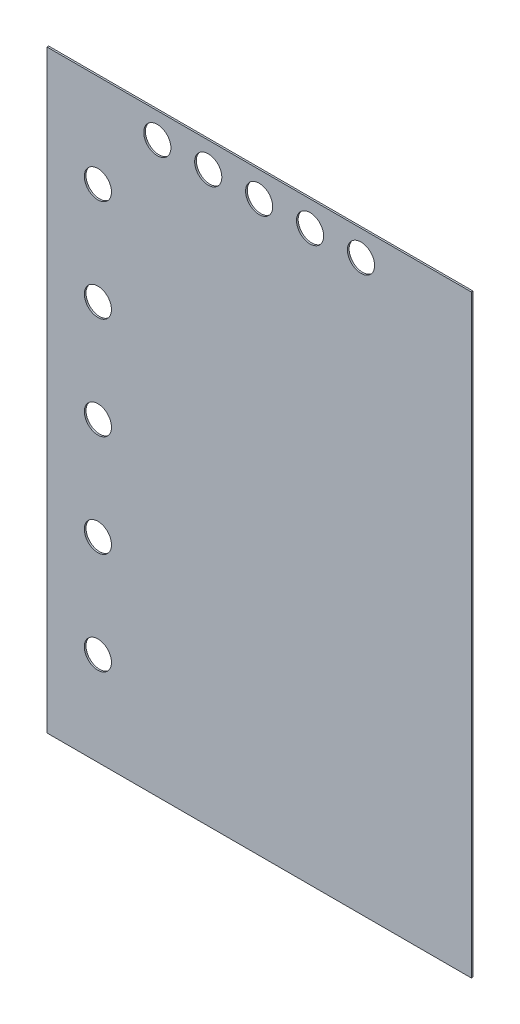
SolidWorks part; units mm, degrees
ref_plane "Front Plane" through (0, 0, 0) normal (1, 0, 0) x (0, 1, 0)
ref_plane "Top Plane" through (0, 0, 0) normal (0, 0, 1) x (0, 1, 0)
ref_plane "Right Plane" through (0, 0, 0) normal (0, 1, 0) x (-1, 0, 0)
sketch "Sketch1" plane through (0, 0, 0) normal (0, 0, 1) x (0, 1, 0)
  line L1 (-175, -125) -> (175, -125)
  line L2 (-175, -125) -> (-175, 125)
  line L3 (-175, 125) -> (175, 125)
  line L4 (175, -125) -> (175, 125)
  line L5 (-175, -125) -> (175, 125) construction
  line L6 (-175, 125) -> (175, -125) construction
  point P0 (0, 0)
  dimension "D1" = 350
  dimension "D2" = 250
extrude "Boss-Extrude1" add sketch "Sketch1" along normal blind 1
sketch "Sketch2" plane through (0, 0, 1) normal (0, 0, 1) x (0, -1, 0)
  line L0 (-160, -125) -> (-160, 125) construction
  line L1 (-175, -125) -> (175, -125) construction
  line L2 (175, 125) -> (-175, 125) construction
  line L3 (-175, 125) -> (-175, -125) construction
  circle A0 centre (-160, -60) radius 8
  circle A1 centre (-160, -30) radius 8
  circle A2 centre (-160, 0) radius 8
  circle A3 centre (-160, 30) radius 8
  circle A4 centre (-160, 60) radius 8
  point P16 (0, 0)
  point P17 (0, 0)
  point P18 (0, 0)
  point P19 (0, 0)
  point P20 (0, 0)
  point P21 (0, 0)
  dimension "D1" = 16
  dimension "D2" = 30
  dimension "D3" = 30
  dimension "D4" = 30
  dimension "D5" = 30
  dimension "D6" = 15
extrude "Cut-Extrude1" cut sketch "Sketch2" against normal through all
sketch "Sketch3" plane through (0, 0, 1) normal (0, 0, 1) x (0, -1, 0)
  line L0 (-175, -125) -> (175, -125) construction
  circle A0 centre (120, -95) radius 8
  circle A1 centre (60, -95) radius 8
  circle A2 centre (0, -95) radius 8
  circle A3 centre (-60, -95) radius 8
  circle A4 centre (-120, -95) radius 8
  point P4 (0, 0)
  point P7 (0, -125)
  dimension "D1" = 16
  dimension "D4" = 5
  dimension "D2" = 30
extrude "Cut-Extrude2" cut sketch "Sketch3" against normal through all
